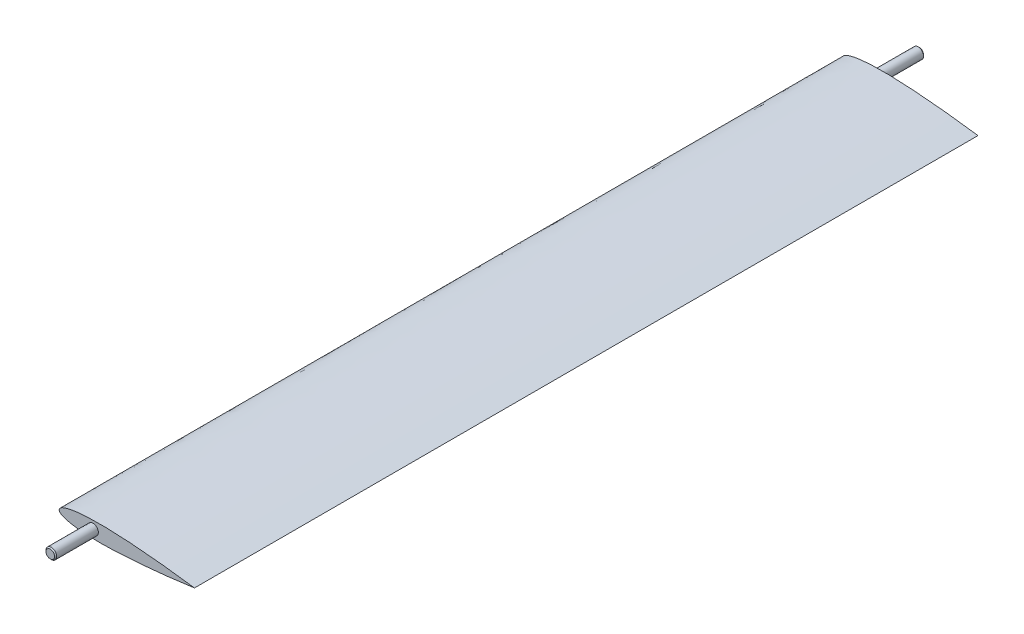
SolidWorks part; units mm, degrees
ref_plane "Front Plane" through (0, 0, 0) normal (0, 0, 1) x (1, 0, 0)
ref_plane "Top Plane" through (0, 0, 0) normal (0, 1, 0) x (1, 0, 0)
ref_plane "Right Plane" through (0, 0, 0) normal (1, 0, 0) x (0, 0, -1)
sketch "Sketch1" plane through (0, 0, 0) normal (0, 0, 1) x (1, 0, 0)
  spline S0 degree 4 poles (0, 0) (0, 0.0338) (0.004, 0.0876) (0.0188, 0.1619) (0.0529, 0.2538) (0.0948, 0.3353) (0.1534, 0.4227) (0.2369, 0.5211) (0.3605, 0.6372) (0.5499, 0.7786) (0.8526, 0.956) (1.3384, 1.1736) (2.127, 1.4362) (3.4448, 1.7454) (5.3549, 2.0271) (7.7765, 2.2199) (10.5668, 2.2987) (13.4676, 2.2726) (16.3652, 2.1673) (19.2618, 2.0014) (21.7904, 1.8152) (23.961, 1.6308) (25.7603, 1.4638) (27.213, 1.32) (28.9963, 1.135) (30.8336, 0.9292) (32.5761, 0.7242) (34.456, 0.4855) (35.7546, 0.3158) (37.5832, 0.0606) (38.6246, -0.0918) (40.1506, -0.3234) (40.8918, -0.4449) (41.4992, -0.5419) (41.6482, -0.5684) (41.8081, -0.5941) knots 0 0 0 0 0 0.003164 0.005066 0.007068 0.009183 0.011752 0.014927 0.019157 0.02508 0.033903 0.047807 0.06905 0.103021 0.160853 0.228932 0.29701 0.365089 0.433167 0.501246 0.569325 0.603364 0.637403 0.671442 0.705482 0.77356 0.8076 0.841639 0.875678 0.909717 0.954859 0.977429 0.988715 1 1 1 1 1 construction
  spline S1 degree 4 poles (0, 0) (0, 0.0338) (0.004, 0.0876) (0.0188, 0.1619) (0.0529, 0.2538) (0.0948, 0.3353) (0.1534, 0.4227) (0.2369, 0.5211) (0.3605, 0.6372) (0.5499, 0.7786) (0.8526, 0.956) (1.3384, 1.1736) (2.127, 1.4362) (3.4448, 1.7454) (5.3549, 2.0271) (7.7765, 2.2199) (10.5668, 2.2987) (13.4676, 2.2726) (16.3652, 2.1673) (19.2618, 2.0014) (21.7904, 1.8152) (23.961, 1.6308) (25.7603, 1.4638) (27.213, 1.32) (28.9963, 1.135) (30.8336, 0.9292) (32.5761, 0.7242) (34.456, 0.4855) (35.7518, 0.3161) (37.0155, 0.1398) (37.6653, 0.047) (37.9889, 0) knots 0 0 0 0 0 0.003164 0.005066 0.007068 0.009183 0.011752 0.014927 0.019157 0.02508 0.033903 0.047807 0.06905 0.103021 0.160853 0.228932 0.29701 0.365089 0.433167 0.501246 0.569325 0.603364 0.637403 0.671442 0.705482 0.77356 0.8076 0.841639 0.875678 0.909427 0.909427 0.909427 0.909427 0.909427
  spline S2 degree 4 poles (0, 0) (0, -0.0338) (0.004, -0.0876) (0.0188, -0.1619) (0.0529, -0.2538) (0.0948, -0.3353) (0.1534, -0.4227) (0.2369, -0.5211) (0.3605, -0.6372) (0.5499, -0.7786) (0.8526, -0.956) (1.3384, -1.1736) (2.127, -1.4362) (3.4448, -1.7454) (5.3549, -2.0271) (7.7765, -2.2199) (10.5668, -2.2987) (13.4676, -2.2726) (16.3652, -2.1673) (19.2618, -2.0014) (21.7904, -1.8152) (23.961, -1.6308) (25.7603, -1.4638) (27.213, -1.32) (28.9963, -1.135) (30.8336, -0.9292) (32.5761, -0.7242) (34.456, -0.4855) (35.7546, -0.3158) (37.5832, -0.0606) (38.6246, 0.0918) (40.1506, 0.3234) (40.8918, 0.4449) (41.4992, 0.5419) (41.6482, 0.5684) (41.8081, 0.5941) knots 0 0 0 0 0 0.003164 0.005066 0.007068 0.009183 0.011752 0.014927 0.019157 0.02508 0.033903 0.047807 0.06905 0.103021 0.160853 0.228932 0.29701 0.365089 0.433167 0.501246 0.569325 0.603364 0.637403 0.671442 0.705482 0.77356 0.8076 0.841639 0.875678 0.909717 0.954859 0.977429 0.988715 1 1 1 1 1 construction
  spline S3 degree 4 poles (0, 0) (0, -0.0338) (0.004, -0.0876) (0.0188, -0.1619) (0.0529, -0.2538) (0.0948, -0.3353) (0.1534, -0.4227) (0.2369, -0.5211) (0.3605, -0.6372) (0.5499, -0.7786) (0.8526, -0.956) (1.3384, -1.1736) (2.127, -1.4362) (3.4448, -1.7454) (5.3549, -2.0271) (7.7765, -2.2199) (10.5668, -2.2987) (13.4676, -2.2726) (16.3652, -2.1673) (19.2618, -2.0014) (21.7904, -1.8152) (23.961, -1.6308) (25.7603, -1.4638) (27.213, -1.32) (28.9963, -1.135) (30.8336, -0.9292) (32.5761, -0.7242) (34.456, -0.4855) (35.7518, -0.3161) (37.0155, -0.1398) (37.6653, -0.047) (37.9889, 0) knots 0 0 0 0 0 0.003164 0.005066 0.007068 0.009183 0.011752 0.014927 0.019157 0.02508 0.033903 0.047807 0.06905 0.103021 0.160853 0.228932 0.29701 0.365089 0.433167 0.501246 0.569325 0.603364 0.637403 0.671442 0.705482 0.77356 0.8076 0.841639 0.875678 0.909427 0.909427 0.909427 0.909427 0.909427
extrude "Boss-Extrude1" add sketch "Sketch1" along normal blind 220
sketch "Sketch6" plane through (0, 0, 0) normal (0, 0, 1) x (1, 0, 0)
  spline S0 degree 4 poles (0, -0.25) (0, -0.2135) (0.0045, -0.1583) (0.0202, -0.0829) (0.0559, 0.0105) (0.0983, 0.0912) (0.1583, 0.1792) (0.2445, 0.279) (0.3727, 0.3974) (0.5692, 0.5414) (0.8849, 0.7226) (1.3947, 0.9456) (2.2248, 1.214) (3.6278, 1.5305) (5.6548, 1.8111) (8.218, 1.9934) (11.1671, 2.0532) (14.2174, 2.0036) (17.2636, 1.8729) (20.309, 1.6801) (22.9666, 1.4698) (25.2488, 1.2635) (27.1389, 1.0782) (28.6686, 0.9183) (30.1605, 0.7557) (31.7144, 0.5748) (33.5365, 0.3564) (35.5523, 0.0925) (37.2418, -0.137) (39.553, -0.4811) (40.6664, -0.6559) (42.2569, -0.9161) (43.0499, -1.057) (43.6793, -1.1661) (43.843, -1.1976) (44.0078, -1.2265) knots 0 0 0 0 0 0.00324 0.004942 0.006838 0.008891 0.01136 0.014425 0.018582 0.024427 0.033056 0.046837 0.068147 0.10216 0.161218 0.229245 0.297273 0.3653 0.433328 0.501355 0.569383 0.603397 0.63741 0.671424 0.705438 0.739452 0.773465 0.841493 0.875507 0.90952 0.95476 0.97738 0.98869 1 1 1 1 1 construction
  spline S1 degree 4 poles (0.0535, 0) (0.0676, 0.0323) (0.0966, 0.0884) (0.1503, 0.1699) (0.2445, 0.279) (0.3727, 0.3974) (0.5692, 0.5414) (0.8849, 0.7226) (1.3947, 0.9456) (2.2248, 1.214) (3.6278, 1.5305) (5.6548, 1.8111) (8.218, 1.9934) (11.1671, 2.0532) (14.2174, 2.0036) (17.2636, 1.8729) (20.309, 1.6801) (22.9666, 1.4698) (25.2488, 1.2635) (27.1389, 1.0782) (28.6686, 0.9183) (30.1605, 0.7557) (31.7144, 0.5748) (33.3534, 0.3783) (34.7466, 0.1977) (35.6668, 0.0753) (36.2182, 0) knots 0.005744 0.005744 0.005744 0.005744 0.005744 0.008891 0.01136 0.014425 0.018582 0.024427 0.033056 0.046837 0.068147 0.10216 0.161218 0.229245 0.297273 0.3653 0.433328 0.501355 0.569383 0.603397 0.63741 0.671424 0.705438 0.739452 0.773465 0.824409 0.824409 0.824409 0.824409 0.824409
  spline S2 degree 4 poles (0.0535, 0) (0.0676, -0.0323) (0.0966, -0.0884) (0.1503, -0.1699) (0.2445, -0.279) (0.3727, -0.3974) (0.5692, -0.5414) (0.8849, -0.7226) (1.3947, -0.9456) (2.2248, -1.214) (3.6278, -1.5305) (5.6548, -1.8111) (8.218, -1.9934) (11.1671, -2.0532) (14.2174, -2.0036) (17.2636, -1.8729) (20.309, -1.6801) (22.9666, -1.4698) (25.2488, -1.2635) (27.1389, -1.0782) (28.6686, -0.9183) (30.1605, -0.7557) (31.7144, -0.5748) (33.3534, -0.3783) (34.7466, -0.1977) (35.6668, -0.0753) (36.2182, 0) knots 0.005744 0.005744 0.005744 0.005744 0.005744 0.008891 0.01136 0.014425 0.018582 0.024427 0.033056 0.046837 0.068147 0.10216 0.161218 0.229245 0.297273 0.3653 0.433328 0.501355 0.569383 0.603397 0.63741 0.671424 0.705438 0.739452 0.773465 0.824409 0.824409 0.824409 0.824409 0.824409
extrude "Cut-Extrude4" cut sketch "Sketch6" along normal through all
sketch "Sketch8" plane through (0, 0, 0) normal (0, 0, 1) x (1, 0, 0)
  spline S0 degree 4 poles (0, 0) (0, 0.0338) (0.004, 0.0876) (0.0188, 0.1619) (0.0529, 0.2538) (0.0948, 0.3353) (0.1534, 0.4227) (0.2369, 0.5211) (0.3605, 0.6372) (0.5499, 0.7786) (0.8526, 0.956) (1.3384, 1.1736) (2.127, 1.4362) (3.4448, 1.7454) (5.3549, 2.0271) (7.7765, 2.2199) (10.5668, 2.2987) (13.4676, 2.2726) (16.3652, 2.1673) (19.2618, 2.0014) (21.7904, 1.8152) (23.961, 1.6308) (25.7603, 1.4638) (27.213, 1.32) (28.9963, 1.135) (30.8336, 0.9292) (32.5761, 0.7242) (34.456, 0.4855) (35.7546, 0.3158) (37.5832, 0.0606) (38.6246, -0.0918) (40.1506, -0.3234) (40.8918, -0.4449) (41.4992, -0.5419) (41.6482, -0.5684) (41.8081, -0.5941) knots 0 0 0 0 0 0.003164 0.005066 0.007068 0.009183 0.011752 0.014927 0.019157 0.02508 0.033903 0.047807 0.06905 0.103021 0.160853 0.228932 0.29701 0.365089 0.433167 0.501246 0.569325 0.603364 0.637403 0.671442 0.705482 0.77356 0.8076 0.841639 0.875678 0.909717 0.954859 0.977429 0.988715 1 1 1 1 1 construction
  spline S1 degree 4 poles (0, 0) (0, 0.0338) (0.004, 0.0876) (0.0188, 0.1619) (0.0529, 0.2538) (0.0948, 0.3353) (0.1534, 0.4227) (0.2369, 0.5211) (0.3605, 0.6372) (0.5499, 0.7786) (0.8526, 0.956) (1.3384, 1.1736) (2.127, 1.4362) (3.4448, 1.7454) (5.3549, 2.0271) (7.7765, 2.2199) (10.5668, 2.2987) (13.4676, 2.2726) (16.3652, 2.1673) (19.2618, 2.0014) (21.7904, 1.8152) (23.961, 1.6308) (25.7603, 1.4638) (27.213, 1.32) (28.9963, 1.135) (30.8336, 0.9292) (32.5761, 0.7242) (34.456, 0.4855) (35.7518, 0.3161) (37.0155, 0.1398) (37.6653, 0.047) (37.9889, 0) knots 0 0 0 0 0 0.003164 0.005066 0.007068 0.009183 0.011752 0.014927 0.019157 0.02508 0.033903 0.047807 0.06905 0.103021 0.160853 0.228932 0.29701 0.365089 0.433167 0.501246 0.569325 0.603364 0.637403 0.671442 0.705482 0.77356 0.8076 0.841639 0.875678 0.909427 0.909427 0.909427 0.909427 0.909427
  spline S2 degree 4 poles (0, 0) (0, -0.0338) (0.004, -0.0876) (0.0188, -0.1619) (0.0529, -0.2538) (0.0948, -0.3353) (0.1534, -0.4227) (0.2369, -0.5211) (0.3605, -0.6372) (0.5499, -0.7786) (0.8526, -0.956) (1.3384, -1.1736) (2.127, -1.4362) (3.4448, -1.7454) (5.3549, -2.0271) (7.7765, -2.2199) (10.5668, -2.2987) (13.4676, -2.2726) (16.3652, -2.1673) (19.2618, -2.0014) (21.7904, -1.8152) (23.961, -1.6308) (25.7603, -1.4638) (27.213, -1.32) (28.9963, -1.135) (30.8336, -0.9292) (32.5761, -0.7242) (34.456, -0.4855) (35.7546, -0.3158) (37.5832, -0.0606) (38.6246, 0.0918) (40.1506, 0.3234) (40.8918, 0.4449) (41.4992, 0.5419) (41.6482, 0.5684) (41.8081, 0.5941) knots 0 0 0 0 0 0.003164 0.005066 0.007068 0.009183 0.011752 0.014927 0.019157 0.02508 0.033903 0.047807 0.06905 0.103021 0.160853 0.228932 0.29701 0.365089 0.433167 0.501246 0.569325 0.603364 0.637403 0.671442 0.705482 0.77356 0.8076 0.841639 0.875678 0.909717 0.954859 0.977429 0.988715 1 1 1 1 1 construction
  spline S3 degree 4 poles (0, 0) (0, -0.0338) (0.004, -0.0876) (0.0188, -0.1619) (0.0529, -0.2538) (0.0948, -0.3353) (0.1534, -0.4227) (0.2369, -0.5211) (0.3605, -0.6372) (0.5499, -0.7786) (0.8526, -0.956) (1.3384, -1.1736) (2.127, -1.4362) (3.4448, -1.7454) (5.3549, -2.0271) (7.7765, -2.2199) (10.5668, -2.2987) (13.4676, -2.2726) (16.3652, -2.1673) (19.2618, -2.0014) (21.7904, -1.8152) (23.961, -1.6308) (25.7603, -1.4638) (27.213, -1.32) (28.9963, -1.135) (30.8336, -0.9292) (32.5761, -0.7242) (34.456, -0.4855) (35.7518, -0.3161) (37.0155, -0.1398) (37.6653, -0.047) (37.9889, 0) knots 0 0 0 0 0 0.003164 0.005066 0.007068 0.009183 0.011752 0.014927 0.019157 0.02508 0.033903 0.047807 0.06905 0.103021 0.160853 0.228932 0.29701 0.365089 0.433167 0.501246 0.569325 0.603364 0.637403 0.671442 0.705482 0.77356 0.8076 0.841639 0.875678 0.909427 0.909427 0.909427 0.909427 0.909427
extrude "Boss-Extrude2" add sketch "Sketch8" along normal blind 3
sketch "Sketch9" plane through (0, 0, 0) normal (0, 0, 1) x (1, 0, 0)
  spline S0 degree 4 poles (0, 0) (0, 0.0338) (0.004, 0.0876) (0.0188, 0.1619) (0.0529, 0.2538) (0.0948, 0.3353) (0.1534, 0.4227) (0.2369, 0.5211) (0.3605, 0.6372) (0.5499, 0.7786) (0.8526, 0.956) (1.3384, 1.1736) (2.127, 1.4362) (3.4448, 1.7454) (5.3549, 2.0271) (7.7765, 2.2199) (10.5668, 2.2987) (13.4676, 2.2726) (16.3652, 2.1673) (19.2618, 2.0014) (21.7904, 1.8152) (23.961, 1.6308) (25.7603, 1.4638) (27.213, 1.32) (28.9963, 1.135) (30.8336, 0.9292) (32.5761, 0.7242) (34.456, 0.4855) (35.7546, 0.3158) (37.5832, 0.0606) (38.6246, -0.0918) (40.1506, -0.3234) (40.8918, -0.4449) (41.4992, -0.5419) (41.6482, -0.5684) (41.8081, -0.5941) knots 0 0 0 0 0 0.003164 0.005066 0.007068 0.009183 0.011752 0.014927 0.019157 0.02508 0.033903 0.047807 0.06905 0.103021 0.160853 0.228932 0.29701 0.365089 0.433167 0.501246 0.569325 0.603364 0.637403 0.671442 0.705482 0.77356 0.8076 0.841639 0.875678 0.909717 0.954859 0.977429 0.988715 1 1 1 1 1 construction
  spline S1 degree 4 poles (0, 0) (0, 0.0338) (0.004, 0.0876) (0.0188, 0.1619) (0.0529, 0.2538) (0.0948, 0.3353) (0.1534, 0.4227) (0.2369, 0.5211) (0.3605, 0.6372) (0.5499, 0.7786) (0.8526, 0.956) (1.3384, 1.1736) (2.127, 1.4362) (3.4448, 1.7454) (5.3549, 2.0271) (7.7765, 2.2199) (10.5668, 2.2987) (13.4676, 2.2726) (16.3652, 2.1673) (19.2618, 2.0014) (21.7904, 1.8152) (23.961, 1.6308) (25.7603, 1.4638) (27.213, 1.32) (28.9963, 1.135) (30.8336, 0.9292) (32.5761, 0.7242) (34.456, 0.4855) (35.7518, 0.3161) (37.0155, 0.1398) (37.6653, 0.047) (37.9889, 0) knots 0 0 0 0 0 0.003164 0.005066 0.007068 0.009183 0.011752 0.014927 0.019157 0.02508 0.033903 0.047807 0.06905 0.103021 0.160853 0.228932 0.29701 0.365089 0.433167 0.501246 0.569325 0.603364 0.637403 0.671442 0.705482 0.77356 0.8076 0.841639 0.875678 0.909427 0.909427 0.909427 0.909427 0.909427
  spline S2 degree 4 poles (0, 0) (0, -0.0338) (0.004, -0.0876) (0.0188, -0.1619) (0.0529, -0.2538) (0.0948, -0.3353) (0.1534, -0.4227) (0.2369, -0.5211) (0.3605, -0.6372) (0.5499, -0.7786) (0.8526, -0.956) (1.3384, -1.1736) (2.127, -1.4362) (3.4448, -1.7454) (5.3549, -2.0271) (7.7765, -2.2199) (10.5668, -2.2987) (13.4676, -2.2726) (16.3652, -2.1673) (19.2618, -2.0014) (21.7904, -1.8152) (23.961, -1.6308) (25.7603, -1.4638) (27.213, -1.32) (28.9963, -1.135) (30.8336, -0.9292) (32.5761, -0.7242) (34.456, -0.4855) (35.7546, -0.3158) (37.5832, -0.0606) (38.6246, 0.0918) (40.1506, 0.3234) (40.8918, 0.4449) (41.4992, 0.5419) (41.6482, 0.5684) (41.8081, 0.5941) knots 0 0 0 0 0 0.003164 0.005066 0.007068 0.009183 0.011752 0.014927 0.019157 0.02508 0.033903 0.047807 0.06905 0.103021 0.160853 0.228932 0.29701 0.365089 0.433167 0.501246 0.569325 0.603364 0.637403 0.671442 0.705482 0.77356 0.8076 0.841639 0.875678 0.909717 0.954859 0.977429 0.988715 1 1 1 1 1 construction
  spline S3 degree 4 poles (0, 0) (0, -0.0338) (0.004, -0.0876) (0.0188, -0.1619) (0.0529, -0.2538) (0.0948, -0.3353) (0.1534, -0.4227) (0.2369, -0.5211) (0.3605, -0.6372) (0.5499, -0.7786) (0.8526, -0.956) (1.3384, -1.1736) (2.127, -1.4362) (3.4448, -1.7454) (5.3549, -2.0271) (7.7765, -2.2199) (10.5668, -2.2987) (13.4676, -2.2726) (16.3652, -2.1673) (19.2618, -2.0014) (21.7904, -1.8152) (23.961, -1.6308) (25.7603, -1.4638) (27.213, -1.32) (28.9963, -1.135) (30.8336, -0.9292) (32.5761, -0.7242) (34.456, -0.4855) (35.7518, -0.3161) (37.0155, -0.1398) (37.6653, -0.047) (37.9889, 0) knots 0 0 0 0 0 0.003164 0.005066 0.007068 0.009183 0.011752 0.014927 0.019157 0.02508 0.033903 0.047807 0.06905 0.103021 0.160853 0.228932 0.29701 0.365089 0.433167 0.501246 0.569325 0.603364 0.637403 0.671442 0.705482 0.77356 0.8076 0.841639 0.875678 0.909427 0.909427 0.909427 0.909427 0.909427
extrude "Boss-Extrude3" add sketch "Sketch9" against normal blind 3 from surface starting at face at (18.9944, 0, 220)
sketch "Sketch10" plane through (0, 0, 0) normal (0, 0, 1) x (1, 0, 0)
  circle A0 centre (9.5, 0) radius 2
sketch "Sketch11" plane through (0, 0, 220) normal (0, 0, 1) x (1, 0, 0)
  circle A0 centre (9.5, 0) radius 1.5
extrude "Boss-Extrude4" add sketch "Sketch11" along normal blind 12
chamfer "Chamfer1" distance 0.3 angle 45 1 edges at (11, 0, 232)
sketch "Sketch12" plane through (0, 0, 0) normal (0, 0, -1) x (-1, 0, 0)
  circle A0 centre (-9.5, 0) radius 1.5
extrude "Boss-Extrude5" add sketch "Sketch12" along normal blind 12
chamfer "Chamfer2" distance 0.3 angle 45 1 edges at (8, 0, -12)
sketch "Sketch14" plane through (0, 0, -12) normal (0, 0, -1) x (-1, 0, 0)
  line L1 (-8.5, 1.7499) -> (-6.3456, 1.7499)
  line L2 (-8.5, 1.7499) -> (-8.5, -1.6159)
  line L3 (-8.5, -1.6159) -> (-6.3456, -1.6159)
  line L4 (-6.3456, 1.7499) -> (-6.3456, -1.6159)
  dimension "D1" = 1
extrude "Cut-Extrude5" cut sketch "Sketch14" against normal blind 6
